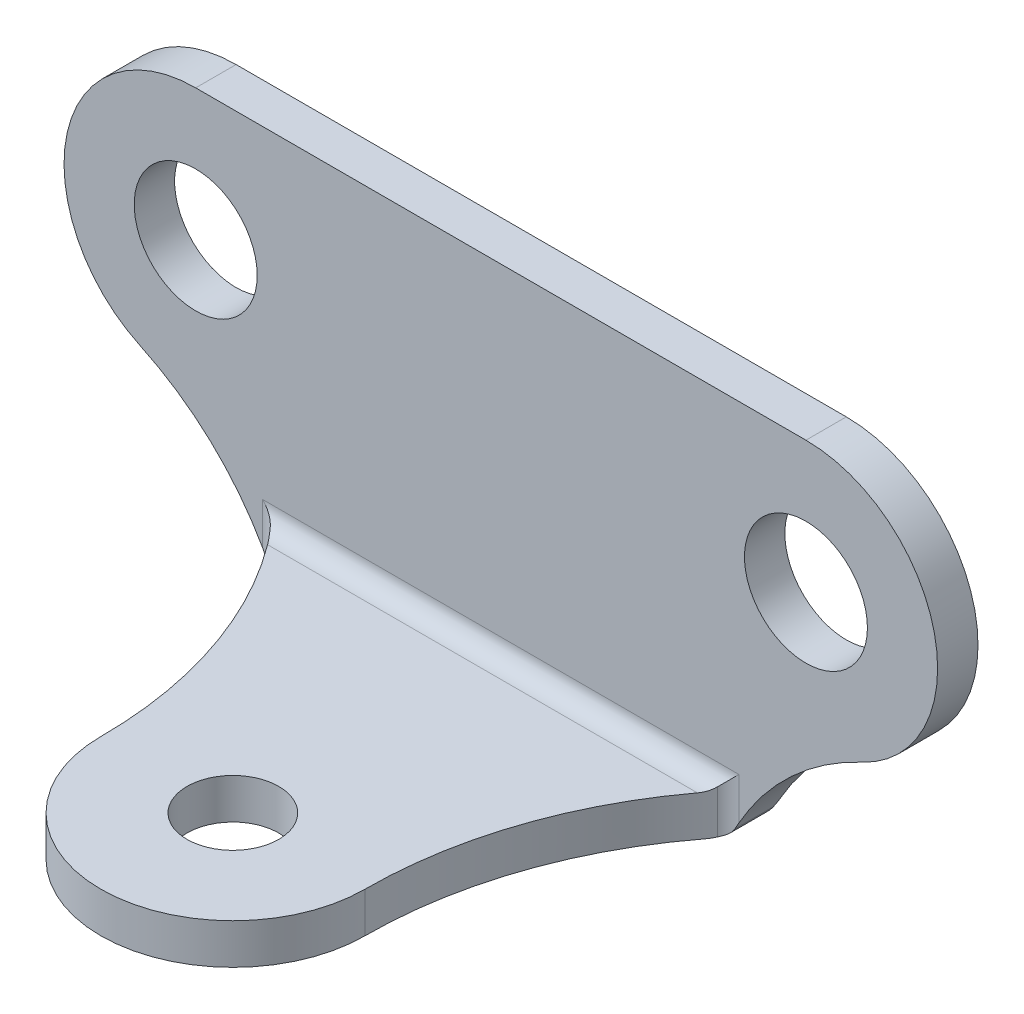
SolidWorks part; units mm, degrees
ref_plane "Plano frontal" through (0, 0, 0) normal (0, 0, 1) x (1, 0, 0)
ref_plane "Plano superior" through (0, 0, 0) normal (0, 1, 0) x (1, 0, 0)
ref_plane "Plano direito" through (0, 0, 0) normal (1, 0, 0) x (0, 0, -1)
sketch "Esboço1" plane through (0, 0, 0) normal (0, 0, 1) x (1, 0, 0)
  line L0 (-16.625, 0) -> (16.625, 0) construction
  line L1 (-16.625, 7.175) -> (16.625, 7.175)
  line L2 (0, 0) -> (0, 7.175) construction
  line L3 (-12.5, -13.625) -> (12.5, -13.625)
  circle A0 centre (-16.625, 0) radius 3.35
  circle A1 centre (16.625, 0) radius 3.35
  arc A2 (-19.6719, -6.4959) -> (-16.625, 7.175) centre (-16.625, 0) cw
  arc A3 (19.6719, -6.4959) -> (16.625, 7.175) centre (16.625, 0) ccw
  arc A4 (-19.6719, -6.4959) -> (-12.5, -13.625) centre (-26.0419, -20.0762) cw
  arc A5 (19.6719, -6.4959) -> (12.5, -13.625) centre (26.0419, -20.0762) ccw
  point P16 (23.8, 0)
  point P20 (-23.8, 0)
  dimension "D2" = 6.7
  dimension "D6" = 15
  dimension "D1" = 33.25
  dimension "D3" = 20.8
  dimension "D4" = 47.6
  dimension "D5" = 25
extrude "Ressalto-extrusão1" add sketch "Esboço1" along normal blind 2.2 contours A5 A3 L1 A2 A4 L3 A1 A0
sketch "Esboço2" plane through (0, 0, 2.2) normal (0, 0, 1) x (1, 0, 0)
  line L1 (-12.5, -13.625) -> (12.5, -13.625)
  line L2 (-12.5, -13.625) -> (-12.5, -11.425)
  line L3 (-12.5, -11.425) -> (12.5, -11.425)
  line L4 (12.5, -13.625) -> (12.5, -11.425)
  line L5 (-12.5, -13.625) -> (12.5, -13.625) construction
  dimension "D1" = 2.2
extrude "Ressalto-extrusão2" add sketch "Esboço2" along normal blind 21.8
sketch "Esboço3" plane through (0, -13.625, 0) normal (0, -1, 0) x (1, 0, 0)
  line L0 (-12.5, 0) -> (12.5, 0) construction
  line L2 (0, 16.8) -> (0, 0) construction
  line L3 (-12.5, 24) -> (12.5, 24) construction
  circle A0 centre (0, 16.8) radius 2.5
  arc A1 (-7.2, 16.8) -> (-12.5, 2.2) centre (-29.9594, 16.8) cw
  arc A2 (-7.2, 16.8) -> (7.2, 16.8) centre (0, 16.8) cw
  arc A3 (7.2, 16.8) -> (12.5, 2.2) centre (29.9594, 16.8) ccw
  dimension "D1" = 5
  dimension "D2" = 16.8
extrude "Corte-extrusão2" cut sketch "Esboço3" against normal blind 24 and the other way through all
fillet "Filete1" radius 1 6 edges at (12.5, -13.625, 1.1) (12.5, -12.525, 2.2) (0, -13.625, 0) (0, -11.425, 2.2)
